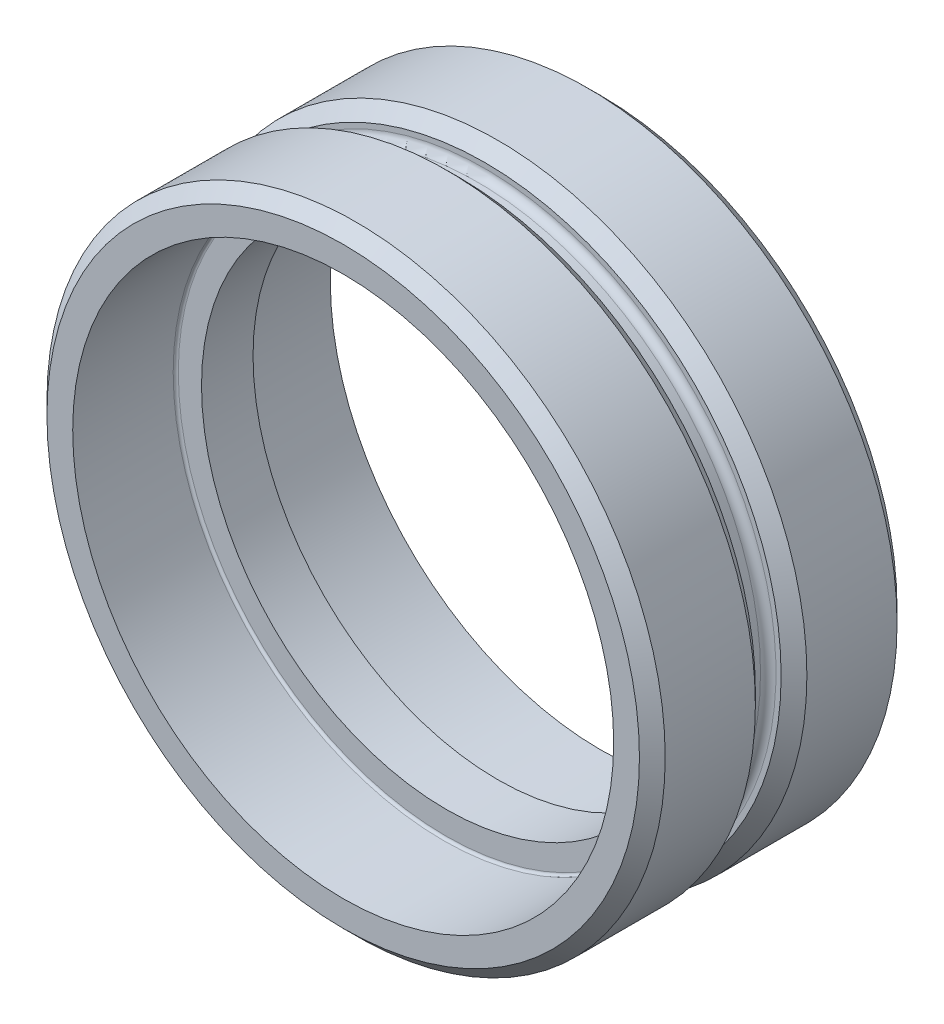
SolidWorks part; units mm, degrees
material "ABS"
ref_plane "Спереди" through (0, 0, 0) normal (0, 0, 1) x (1, 0, 0)
ref_plane "Сверху" through (0, 0, 0) normal (0, 1, 0) x (1, 0, 0)
ref_plane "Справа" through (0, 0, 0) normal (1, 0, 0) x (0, 0, -1)
sketch "Эскиз18" plane through (0, 0, 0) normal (1, 0, 0) x (0, 0, -1)
  line L0 (0, 0) -> (-13.7701, 0) construction
  line L2 (-10, -10.5) -> (-6, -10.5)
  line L3 (-6, -10.5) -> (-6, -9.5)
  line L4 (-6, -9.5) -> (-4, -9.5)
  line L5 (-4, -9.5) -> (-4, -10.5)
  line L6 (-4, -10.5) -> (0, -10.5)
  line L7 (-10, -12) -> (-10, -10.5)
  line L13 (0, -12) -> (0, -10.5)
  line L14 (-5, -9.5) -> (-5, -18.1745) construction
  line L15 (0, -12) -> (-4.5, -12)
  line L16 (-4.5, -12) -> (-4.5, -11)
  line L17 (-4.5, -11) -> (-5.5, -11)
  line L18 (-5.5, -11) -> (-5.5, -12)
  line L19 (-5.5, -12) -> (-10, -12)
  dimension "D1" = 24
  dimension "D2" = 21
  dimension "D3" = 4
  dimension "D4" = 10
  dimension "D5" = 4
  dimension "D6" = 1
  dimension "D7" = 1
  dimension "D9" = 1
revolve "Повернуть1" add sketch "Эскиз18" angle 360 about L0
fillet "Скругление1" radius 0.3 2 edges at (-11, 0, 4.5) (-11, 0, 5.5)
chamfer "Фаска1" distance 0.5 angle 45 4 edges at (-12, 0, 4.5) (-12, 0, 0) (-12, 0, 10) (-12, 0, 5.5)
fillet "Скругление2" radius 0.1 2 edges at (-10.5, 0, 6) (-10.5, 0, 4)
